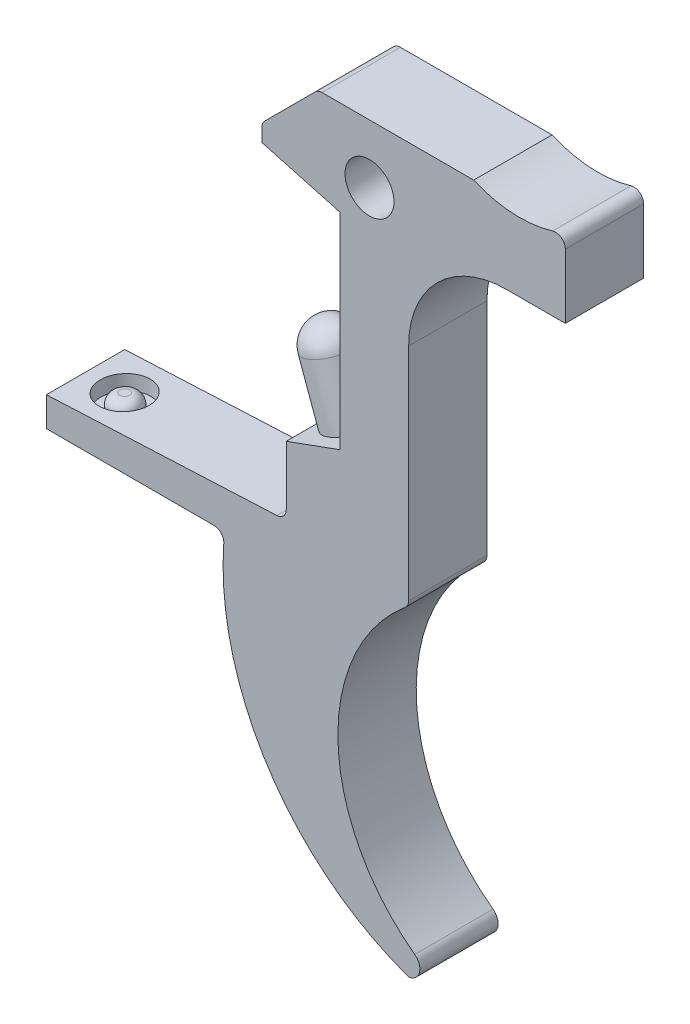
SolidWorks part; units mm, degrees
ref_plane "정면" through (0, 0, 0) normal (0, 0, 1) x (1, 0, 0)
ref_plane "윗면" through (0, 0, 0) normal (0, 1, 0) x (1, 0, 0)
ref_plane "우측면" through (0, 0, 0) normal (1, 0, 0) x (0, 0, -1)
sketch "스케치1" plane through (0, 0, 0) normal (0, 0, 1) x (1, 0, 0)
  line L0 (-8.5, -26.6754) -> (5.7296, -26.6754) construction
  line L1 (-11, 0.25) -> (-5.25, 6)
  line L2 (10.6459, 6) -> (-5.25, 6)
  line L3 (-11, 0.25) -> (-11, -1.4939)
  line L5 (-3, -3.6736) -> (-3, -24.6736)
  line L6 (-3, -24.6736) -> (-8.5, -26.6754)
  line L7 (-8.5, -26.6754) -> (-8.5, -33.6754)
  line L9 (-33, -37.8094) -> (-33, -34.8094)
  line L10 (-33, -37.8094) -> (-14.7854, -37.8094)
  line L11 (-11, -1.4939) -> (-3, -3.6736)
  line L13 (-33, -34.8094) -> (-8.5, -33.6754)
  line L18 (4, -35) -> (4, -12)
  line L19 (14, -2) -> (20, -2)
  line L20 (20, -2) -> (20, 6)
  circle A0 centre (0, 0) radius 2.5
  arc A1 (4, -12) -> (14, -2) centre (14, -12) cw
  arc A2 (4, -35) -> (4.6203, -65.4955) centre (15.9776, -50.0104) ccw
  arc A3 (4, -67.8094) -> (4.6203, -65.4955) centre (3.8602, -66.5318) ccw
  arc A4 (20, 6) -> (10.6459, 6) centre (15.3229, 16.7722) cw
  arc A5 (4, -67.8094) -> (-14.7854, -37.8094) centre (13.6308, -40.8973) cw
  point P25 (4, -2)
  point P32 (-11, 6)
  dimension "D1" = 5
  dimension "D15" = 10
  dimension "D21" = 19.2035
  dimension "D22" = 3
  dimension "D2" = 20
  dimension "D3" = 33
  dimension "D4" = 31
  dimension "D6" = 8
  dimension "D7" = 6
  dimension "D8" = 21
  dimension "D9" = 5.5
  dimension "D10" = 7
  dimension "D11" = 9.3541
  dimension "D12" = 20
  dimension "D13" = 16
extrude "보스-돌출1" add sketch "스케치1" along normal blind 8 contours L0 L7 L10 A3 A2 L18 | L6 L0 L18 A1 L19 L20 L2 L3 L5 A0 region at (3.2798, -5.6784, 0) region at (-7.8139, -42.7856, 0)
sketch "스케치2" plane through (-3, 0, 0) normal (-1, 0, 0) x (0, 0, 1)
  line L0 (4, -3.6736) -> (4, -9.6736) construction
  circle A0 centre (4, -9.6736) radius 2.5
  dimension "D1" = 5
  dimension "D2" = 6
fillet "필렛8" radius 1 3 edges at (-8.5, -33.6754, 4) (-14.7854, -37.8094, 4) (4, -35, 4)
extrude "보스-돌출2" add sketch "스케치2" along normal blind 2.5
fillet "필렛7" radius 2.5 1 edges at (-5.5, -12.1736, 4)
sketch "스케치3" plane through (7.579, -20.8231, 0) normal (-0.342, 0.9397, 0) x (0.9397, 0.342, 0)
  line L0 (-11.2579, 0) -> (-17.1109, -8) construction
  circle A0 centre (-14.1844, -4) radius 2.5
  dimension "D1" = 5
extrude "보스-돌출3" add sketch "스케치3" along normal blind 8.7
fillet "필렛4" radius 2.5 1 edges at (-11.0748, -18.3542, 4)
fillet "필렛5" radius 1 1 edges at (20, 6, 4)
fillet "필렛6" radius 1 2 edges at (-5.25, 6, 4) (-11, 0.25, 4)
sketch "스케치4" plane through (0, -2, 0) normal (0, -1, 0) x (1, 0, 0)
  circle A0 centre (16.726, 4) radius 2.5
  dimension "D1" = 5
extrude "컷-돌출1" cut sketch "스케치4" against normal blind 3
sketch "스케치5" plane through (1.5372, -33.2109, 0) normal (-0.0462, 0.9989, 0) x (0.9989, 0.0462, 0)
  line L0 (-34.5741, -8) -> (-34.5741, 0) construction
  circle A0 centre (-30.5741, -4) radius 2.5
  point P0 (-34.5741, -4)
  dimension "D1" = 5
  dimension "D2" = 4
extrude "컷-돌출2" cut sketch "스케치5" against normal blind 1.5
sketch "스케치7" plane through (1.6065, -34.7093, 0) normal (-0.0462, 0.9989, 0) x (0.9989, 0.0462, 0)
  circle A0 centre (-30.5741, -4) radius 1.5
extrude "보스-돌출4" add sketch "스케치7" along normal blind 1.5
fillet "필렛9" radius 1 1 edges at (-30.5027, -34.6938, 4)
